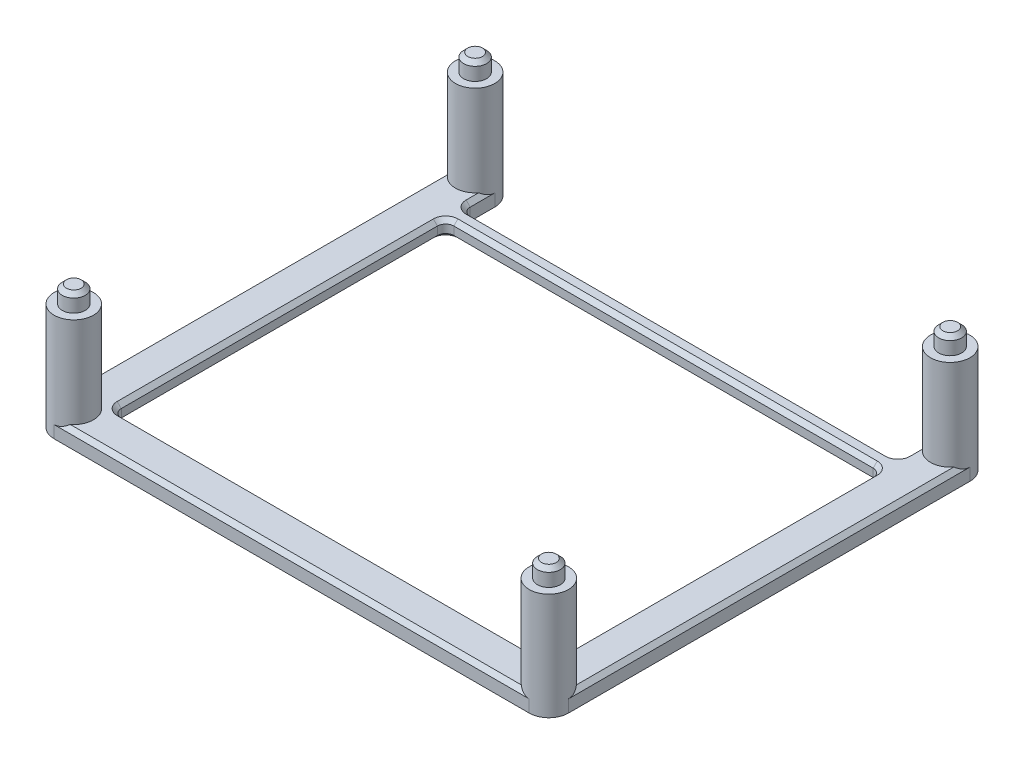
SolidWorks part; units mm, degrees
ref_plane "Front Plane" through (0, 0, 0) normal (0, 0, 1) x (1, 0, 0)
ref_plane "Top Plane" through (0, 0, 0) normal (0, 1, 0) x (1, 0, 0)
ref_plane "Right Plane" through (0, 0, 0) normal (1, 0, 0) x (0, 0, -1)
sketch "Sketch1" plane through (0, 0, 0) normal (0, 1, 0) x (1, 0, 0)
  line L0 (2.55, 49) -> (2.55, 46) construction
  line L1 (0, 0) -> (58, 0) construction
  line L2 (0, 0) -> (0, 49) construction
  line L3 (0, 49) -> (58, 49) construction
  line L4 (58, 0) -> (58, 49) construction
  line L5 (2.55, 46) -> (55.25, 46) construction
  line L6 (55.25, 46) -> (55.25, 49) construction
  line L7 (2.4, 49) -> (2.4, 46)
  line L8 (3.4, 45) -> (54.6, 45)
  line L9 (55.6, 46) -> (55.6, 49)
  line L10 (-2.4, 49) -> (-2.4, 0)
  line L11 (0, -2.4) -> (58, -2.4)
  line L12 (60.4, 0) -> (60.4, 49)
  line L14 (3.4, 43) -> (54.6, 43)
  line L15 (2.4, 42) -> (2.4, 3.4)
  line L16 (3.4, 2.4) -> (54.6, 2.4)
  line L17 (55.6, 42) -> (55.6, 3.4)
  circle A0 centre (0, 49) radius 2.4 construction
  circle A1 centre (58, 49) radius 2.4 construction
  circle A2 centre (58, 0) radius 2.4 construction
  circle A3 centre (0, 0) radius 2.4 construction
  arc A4 (-2.4, 49) -> (2.4, 49) centre (0, 49) cw
  arc A5 (55.6, 49) -> (60.4, 49) centre (58, 49) cw
  arc A6 (60.4, 0) -> (58, -2.4) centre (58, 0) cw
  arc A7 (-2.4, 0) -> (0, -2.4) centre (0, 0) ccw
  arc A8 (3.4, 2.4) -> (2.4, 3.4) centre (3.4, 3.4) cw
  arc A9 (2.4, 42) -> (3.4, 43) centre (3.4, 42) cw
  arc A10 (54.6, 2.4) -> (55.6, 3.4) centre (54.6, 3.4) ccw
  arc A11 (55.6, 42) -> (54.6, 43) centre (54.6, 42) ccw
  arc A12 (55.6, 46) -> (54.6, 45) centre (54.6, 46) cw
  arc A13 (3.4, 45) -> (2.4, 46) centre (3.4, 46) cw
  dimension "D3" = 4.8
  dimension "D4" = 2.55
  dimension "D10" = 1
  dimension "D1" = 58
  dimension "D2" = 49
  dimension "D5" = 2.75
  dimension "D6" = 3
  dimension "D7" = 1
  dimension "D8" = 4.8
  dimension "D9" = 2
extrude "Retainer" add sketch "Sketch1" along normal blind 2
sketch "Sketch2" plane through (0, 2, 0) normal (0, 1, 0) x (1, 0, 0)
  circle A0 centre (0, 49) radius 2.4
  circle A1 centre (58, 49) radius 2.4
  circle A2 centre (58, 0) radius 2.4
  circle A3 centre (0, 0) radius 2.4
  arc A4 (2.4, 49) -> (-2.4, 49) centre (0, 49) ccw construction
  arc A5 (60.4, 49) -> (55.6, 49) centre (58, 49) ccw construction
  arc A6 (-2.4, 0) -> (0, -2.4) centre (0, 0) ccw construction
  arc A7 (58, -2.4) -> (60.4, 0) centre (58, 0) ccw construction
extrude "Raisers" add sketch "Sketch2" along normal blind 11.07
sketch "Sketch3" plane through (0, 13.07, 0) normal (0, 1, 0) x (1, 0, 0)
  circle A0 centre (0, 49) radius 1.4
  circle A1 centre (58, 49) radius 1.4
  circle A2 centre (58, 0) radius 1.4
  circle A3 centre (0, 0) radius 1.4
  dimension "D1" = 2.8
extrude "Pins" add sketch "Sketch3" along normal blind 2.1
chamfer "Pin Chamfers" distance 0.5 angle 45 4 edges at (0, 15.17, 1.4) (58, 15.17, 1.4) (58, 15.17, -47.6) (0, 15.17, -47.6)
chamfer "Shell Chamfer" distance 0.5 angle 45 24 edges at (2.6929, 0, -2.6929) (2.4, 0, -22.7) (2.6929, 0, -42.7071) (29, 0, -43) (55.3071, 0, -42.7071) (29, 0, -2.4) (55.6, 0, -22.7) (55.3071, 0, -2.6929) (55.3071, 2, -2.6929) (55.6, 2, -22.7) (55.3071, 2, -42.7071) (29, 2, -2.4) (2.6929, 2, -2.6929) (29, 2, -43) (2.4, 2, -22.7) (2.6929, 2, -42.7071) (-2.4, 2, -24.5) (29, 2, 2.4) (60.4, 2, -24.5) (55.6, 2, -47.5) (55.3071, 2, -45.2929) (29, 2, -45) (2.6929, 2, -45.2929) (2.4, 2, -47.5)
